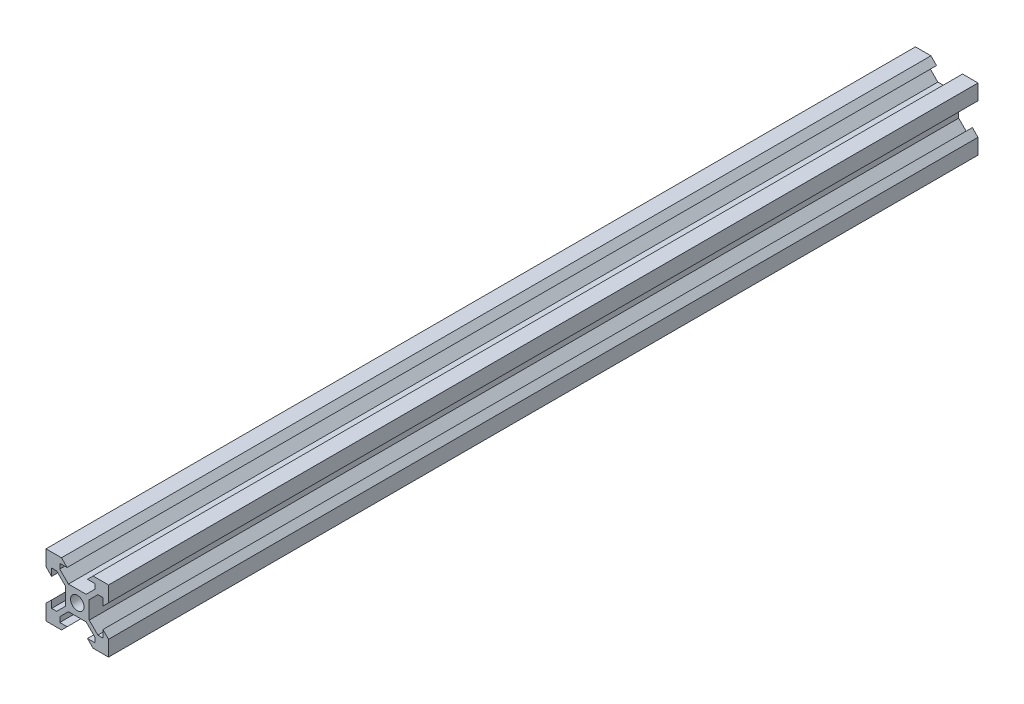
SolidWorks part; units mm, degrees
ref_plane "Alzado" through (0, 0, 0) normal (0, 0, 1) x (1, 0, 0)
ref_plane "Planta" through (0, 0, 0) normal (0, 1, 0) x (1, 0, 0)
ref_plane "Vista lateral" through (0, 0, 0) normal (1, 0, 0) x (0, 0, -1)
sketch "Croquis1" plane through (0, 0, 0) normal (0, 0, 1) x (1, 0, 0)
  line L0 (0, 0) -> (0, -20) construction
  line L2 (0, 0) -> (0, -0.5674)
  line L5 (6.175, -7.1649) -> (6.175, -12.8351)
  line L6 (7.1649, -13.825) -> (12.8351, -13.825)
  line L7 (13.825, -7.1649) -> (13.825, -12.8351)
  line L8 (7.1649, -6.175) -> (12.8351, -6.175)
  line L9 (6.175, -13.825) -> (13.825, -13.825) construction
  line L10 (13.825, -6.175) -> (13.825, -13.825) construction
  line L12 (10, -10) -> (32.1172, -10) construction
  line L13 (13.25, -18.2) -> (15.05, -20)
  line L14 (20, -20) -> (15.6, -20)
  line L15 (20, -20) -> (20, -15.6)
  line L16 (18.2, -15.6) -> (16.5899, -15.6)
  line L32 (15.6, -18.2) -> (15.6, -16.5899)
  line L33 (10, -10) -> (10, -23.2493) construction
  line L34 (4.4, -18.2) -> (4.4, -16.5899)
  line L35 (7.1649, -13.825) -> (4.4, -16.5899)
  line L36 (15.6, -18.2) -> (13.25, -18.2)
  line L38 (15.6, -20) -> (15.05, -20)
  line L40 (15.05, -20) -> (20, -20)
  line L41 (0, -20) -> (20, -20) construction
  line L42 (6.175, -12.8351) -> (3.4101, -15.6)
  line L43 (18.2, -13.25) -> (20, -15.05)
  line L44 (20, -20) -> (18.2, -20)
  line L45 (20, -20) -> (20, -15.05)
  line L48 (20, -15.05) -> (20, -20)
  line L49 (20, 0) -> (20, -20) construction
  line L50 (18.2, -15.6) -> (18.2, -13.25)
  line L51 (12.8351, -13.825) -> (15.6, -16.5899)
  line L52 (13.825, -12.8351) -> (16.5899, -15.6)
  line L53 (1.8, -15.6) -> (3.4101, -15.6)
  line L54 (1.8, -15.6) -> (1.8, -13.25)
  line L55 (1.8, -13.25) -> (0, -15.05)
  line L56 (0, 0) -> (20, 0) construction
  line L57 (0, -20) -> (0, -15.6)
  line L58 (0, -15.6) -> (0, -15.05)
  line L59 (0, -20) -> (4.4, -20)
  line L60 (0, -20) -> (4.95, -20)
  line L61 (6.75, -18.2) -> (4.95, -20)
  line L62 (4.4, -18.2) -> (6.75, -18.2)
  line L63 (1.8, -4.4) -> (3.4101, -4.4)
  line L64 (6.175, -7.1649) -> (3.4101, -4.4)
  line L65 (7.1649, -6.175) -> (4.4, -3.4101)
  line L66 (4.4, -1.8) -> (4.4, -3.4101)
  line L67 (4.4, -1.8) -> (6.75, -1.8)
  line L68 (6.75, -1.8) -> (4.95, 0)
  line L69 (0, 0) -> (4.4, 0)
  line L70 (4.4, 0) -> (4.95, 0)
  line L71 (0, 0) -> (0, -4.4)
  line L72 (0, 0) -> (0, -4.95)
  line L73 (1.8, -6.75) -> (0, -4.95)
  line L74 (1.8, -4.4) -> (1.8, -6.75)
  line L75 (15.6, -1.8) -> (15.6, -3.4101)
  line L76 (12.8351, -6.175) -> (15.6, -3.4101)
  line L77 (13.825, -7.1649) -> (16.5899, -4.4)
  line L78 (18.2, -4.4) -> (16.5899, -4.4)
  line L79 (18.2, -4.4) -> (18.2, -6.75)
  line L80 (18.2, -6.75) -> (20, -4.95)
  line L81 (20, 0) -> (20, -4.4)
  line L82 (20, -4.4) -> (20, -4.95)
  line L83 (20, 0) -> (15.6, 0)
  line L84 (20, 0) -> (15.05, 0)
  line L85 (13.25, -1.8) -> (15.05, 0)
  line L86 (15.6, -1.8) -> (13.25, -1.8)
  line L87 (6.175, -6.175) -> (13.825, -6.175) construction
  line L88 (6.175, -6.175) -> (6.175, -13.825) construction
  circle A0 centre (10, -10) radius 2.15
  point P69 (10, -10)
  dimension "D3" = 4.3
  dimension "D2" = 4
  dimension "D11" = 4.4
  dimension "D15" = 4.4
  dimension "D16" = 6.75
extrude "Saliente-Extruir2" add sketch "Croquis1" along normal blind 278 contours L86 L75 L76 L8 L65 L66 L67 L68 L70 L69 L2 L71 L72 L73 L74 L63 L64 L5 L42 L53 L54 L55 L58 L57 L59 L60 L61 L62 L34 L35 L6 L51 L32 L36 L13 L38 L40 L14 L15 L45 L43 L50 L16 L52 L7 L77 L78 L79 L80 L82 L81 region at (2.2, -0.2828, 0)
